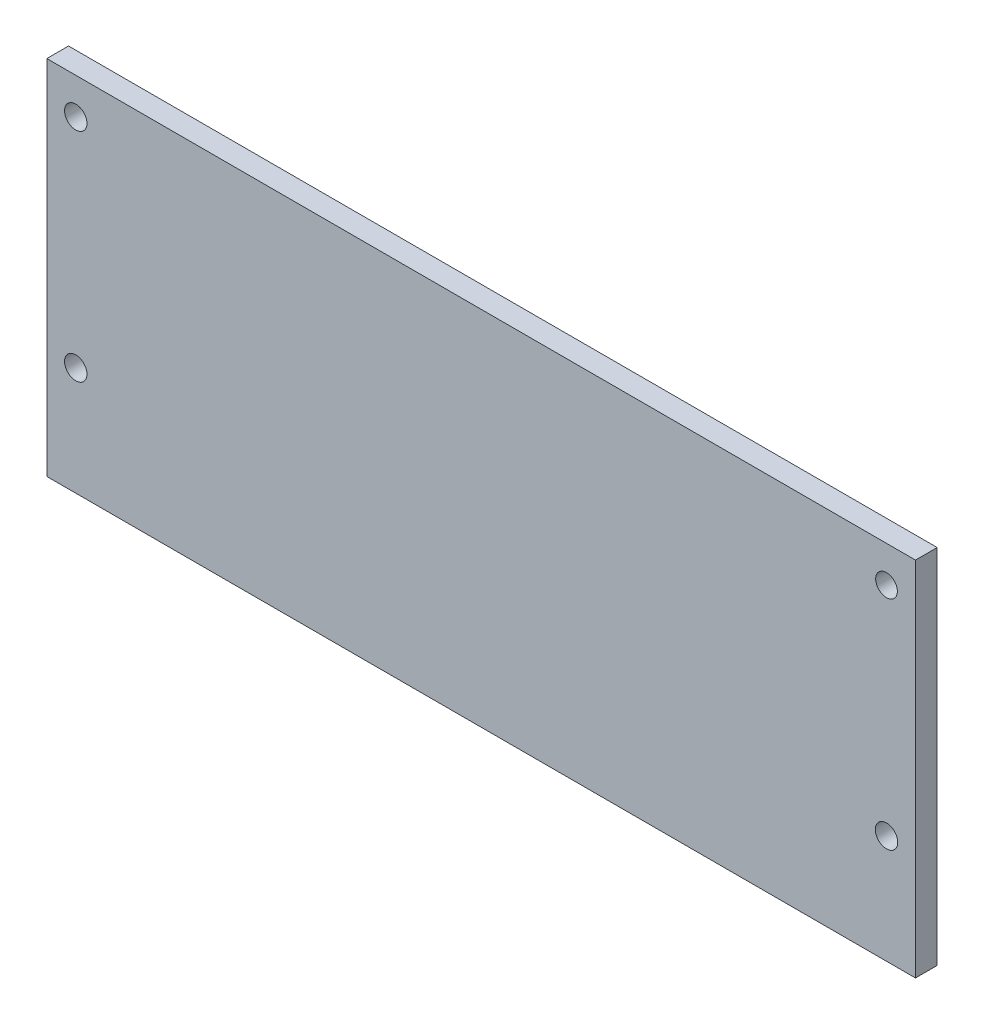
SolidWorks part; units mm, degrees
ref_plane "前视基准面" through (0, 0, 0) normal (0, 0, 1) x (1, 0, 0)
ref_plane "上视基准面" through (0, 0, 0) normal (0, 1, 0) x (1, 0, 0)
ref_plane "右视基准面" through (0, 0, 0) normal (1, 0, 0) x (0, 0, -1)
other "Configuration Table"
sketch "草图1" plane through (0, 0, 0) normal (0, 0, 1) x (1, 0, 0)
  line L1 (60, -25) -> (-60, -25)
  line L2 (60, -25) -> (60, 25)
  line L3 (60, 25) -> (-60, 25)
  line L4 (-60, -25) -> (-60, 25)
  line L5 (60, -25) -> (-60, 25) construction
  line L6 (60, 25) -> (-60, -25) construction
  point P0 (0, 0)
  dimension "D1" = 120
  dimension "D2" = 50
extrude "凸台-拉伸1" add sketch "草图1" along normal blind 3
sketch "草图3" plane through (0, 0, 0) normal (0, 0, -1) x (-1, 0, 0)
  line L2 (60, 25) -> (60, -25) construction
  line L3 (-60, 25) -> (60, 25) construction
  line L5 (-60, -25) -> (-60, 25) construction
  circle A0 centre (-56, 20) radius 1.5
  circle A1 centre (56, 20) radius 1.55
  dimension "D1" = 4
  dimension "D2" = 5
  dimension "D3" = 4
  dimension "D4" = 5
extrude "切除-拉伸2" cut sketch "草图3" against normal blind 10
sketch "草图4" plane through (0, 0, 3) normal (0, 0, 1) x (1, 0, 0)
  line L0 (-56, 20) -> (-56, -10) construction
  line L1 (56, 20) -> (56, -10) construction
  circle A0 centre (-56, -10) radius 1.55
  circle A1 centre (56, -10) radius 1.55
  dimension "D1" = 3.1
  dimension "D3" = 30
  dimension "D4" = 3.1
  dimension "D2" = 30
extrude "切除-拉伸3" cut sketch "草图4" against normal blind 10 contours A0 | A1
